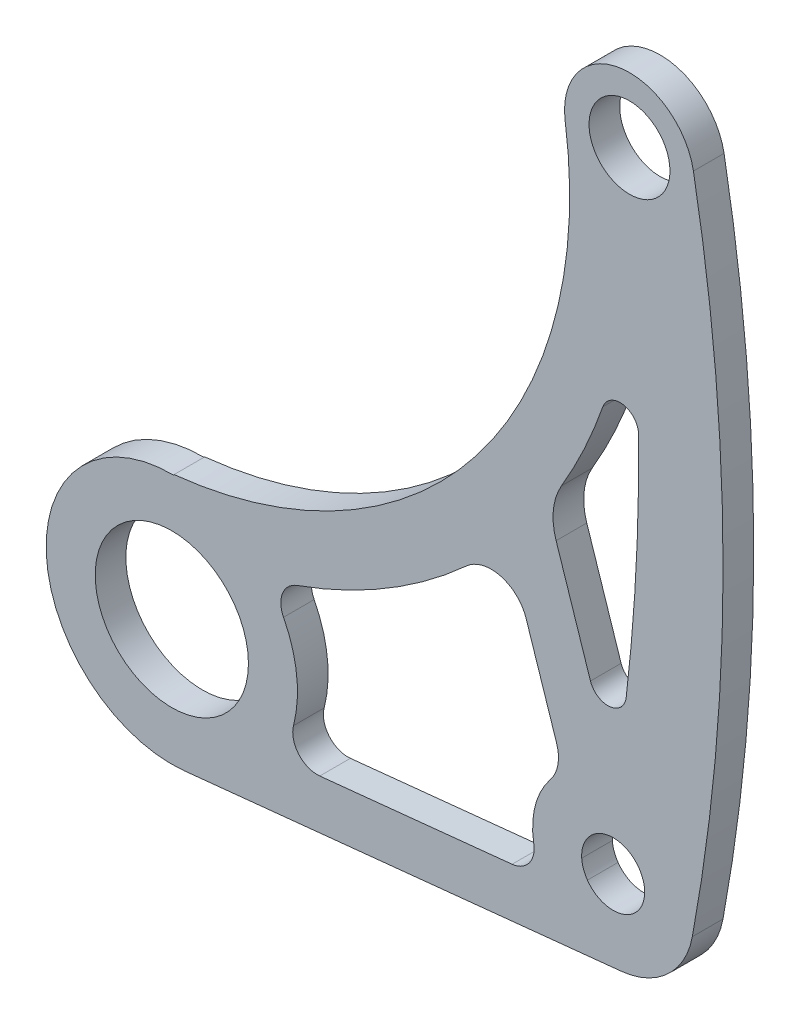
SolidWorks part; units mm, degrees
material "6061-T6 (SS)"
ref_plane "Front Plane" through (0, 0, 0) normal (0, 0, 1) x (1, 0, 0)
ref_plane "Top Plane" through (0, 0, 0) normal (0, 1, 0) x (1, 0, 0)
ref_plane "Right Plane" through (0, 0, 0) normal (1, 0, 0) x (0, 0, -1)
sketch "Sketch2" plane through (0, 0, 0) normal (0, 0, 1) x (1, 0, 0)
  line L0 (0, 0) -> (45.72, 0) construction
  line L1 (45.72, 0) -> (47.4133, 66.0183) construction
  line L2 (47.4133, 66.0183) -> (0, 0) construction
  line L3 (-9.9543, 8.3886) -> (42.2663, 70.3558)
  line L4 (54.1443, 66.0101) -> (54.0639, -0.0102)
  line L5 (46.5729, -8.3002) -> (1.3307, -12.9493)
  line L6 (-6.2268, 4.9225) -> (44.1256, 68.6173)
  line L7 (0.8114, -7.8959) -> (46.0536, -3.2468)
  line L8 (48.9813, -0.1295) -> (51.601, 65.852)
  line L9 (0, 0) -> (16.2847, -19.4928) construction
  line L10 (45.72, 0) -> (38.8832, 9.7026) construction
  line L11 (45.72, 0) -> (42.0108, 11.275) construction
  line L12 (45.72, 0) -> (44.9726, 11.8459) construction
  line L13 (47.2407, 59.2895) -> (45.9339, 8.3412)
  line L14 (45.72, 0) -> (36.8585, 26.9366) construction
  line L15 (34.7499, 24.3546) -> (40.5957, 6.585)
  line L16 (38.8824, 29.7758) -> (45.9339, 8.3412)
  line L17 (41.2892, 13.4683) -> (38.6201, 12.5902) construction
  line L18 (41.2892, 13.4683) -> (43.9584, 14.3464) construction
  circle A0 centre (0, 0) radius 7.9375
  circle A1 centre (45.72, 0) radius 3.2639
  circle A2 centre (47.4133, 66.0183) radius 4.191
  circle A3 centre (0, 0) radius 13.0175
  circle A4 centre (45.72, 0) radius 8.3439
  circle A5 centre (47.4133, 66.0183) radius 6.731
  circle A8 centre (-4.5053, 58.5645) radius 45.72
  circle A9 centre (-4.5053, 58.5645) radius 52.07
  circle A10 centre (-133.3933, 33.155) radius 190.5
  circle A11 centre (-142.1385, 38.656) radius 190.5
  point P29 (47.2407, 59.2895)
  point P30 (45.72, 0)
  dimension "D1" = 8.382
  dimension "D2" = 6.5278
  dimension "D3" = 15.875
  dimension "D13" = 381
  dimension "D14" = 381
  dimension "D17" = 91.44
  dimension "2.7" = 45.72
  dimension "D5" = 66.04
  dimension "D6" = 5.08
  dimension "D7" = 2.54
  dimension "D8" = 5.08
  dimension "D9" = 81.28
  dimension "D4" = 54.83
  dimension "D10" = 71.79
  dimension "D11" = 86.39
  dimension "D12" = 6.35
  dimension "D15" = 25.4
  dimension "D16" = 50.124
extrude "Boss-Extrude1" add sketch "Sketch2" along normal blind 3.175 contours A3 A9 L13 A5 L6 A8 | A4 A10 A5 L4 | A5 L8 A4 L4 | A11 A4 L8 A5 A9 | A11 A9 A5 | A9 A11 L13 | A9 A5 L8 A2 | A11 A5 A9 A2 | A9 A2 L8 A5 | A2 A11 A5 L6 | A11 A2 A9 A5 | A5 A11 A2 L6 | L6 A9 A0 A3 | A3 A9 L6 | A9 A3 L7 A0 L6 | A9 L6 A0 | A9 A0 L7 A3 | L5 A11 A4 L7 A3 | A11 L5 A4 | A11 A4 L8 A1 L7 | A4 A11 L7 | L7 A11 A1 A4 | A11 L7 A1 | A11 A1 L8 A4 | A8 L6 A5 | A9 L15 A4 L16 region at (-5.5006, 9.4923, 0) region at (-8.0357, 6.3009, 0) region at (2.6571, 9.723, 0) region at (29.9998, 27.4659, 0) region at (24.338, -8.1937, 0) region at (-5.1584, 6.1188, 0) region at (43.0257, 68.9495, 0) region at (40.821, 64.6173, 0) region at (9.2487, 0.3015, 0) region at (43.5135, -8.326, 0) region at (45.793, 71.1308, 0) region at (50.931, 71.5823, 0) region at (43.84, 62.6006, 0) region at (40.0789, 17.433, 0) region at (49.3721, -2.053, 0) region at (41.3953, -5.2292, 0) region at (41.276, 2.0979, 0) region at (55.3056, 32.9236, 0) region at (47.2719, 55.385, 0) region at (47.3007, 60.6601, 0) region at (47.4506, 58.3343, 0) region at (44.3051, -3.1823, 0) region at (49.6572, 61.3283, 0) region at (49.0359, 35.0199, 0) region at (47.419, 5.2185, 0) region at (52.2253, 31.0661, 0)
ref_plane "Plane2" through (45.72, 0, 0) normal (-0.576, 0.8174, 0) x (0.8174, 0.576, 0)
split line "Split Line2"
ref_plane "Plane3" through (45.72, 0, 0) normal (-0.063, 0.998, 0) x (0.998, 0.063, 0)
split line "Split Line3"
fillet "Fillet1" radius 2.54 3 edges at (11.0749, -6.8412, 1.5875) (38.4148, -4.0318, 1.5875) (9.8489, 8.5121, 1.5875)
fillet "Fillet2" radius 3.81 2 edges at (40.5957, 6.585, 1.5875) (34.7499, 24.3546, 1.5875)
fillet "Fillet3" radius 1.905 2 edges at (45.9339, 8.3412, 1.5875) (47.5238, 56.5014, 1.5875)
fillet "Fillet4" radius 6.35 1 edges at (38.8824, 29.7758, 1.5875)
equation "\"Droop angle\"= 54.83"
equation "\"Static angle\"= 71.79"
equation "\"Jounce angle\"= 86.39"
equation "\"D4@Sketch2\"=\"Droop angle\""
equation "\"D10@Sketch2\"=\"Static angle\""
equation "\"D11@Sketch2\"=\"Jounce angle\""
equation "\"DL Rocker Angle\"= 50.124deg"
equation "\"DL Rocker Length\"= 1.0in"
equation "\"D15@Sketch2\"=\"DL Rocker Length\""
